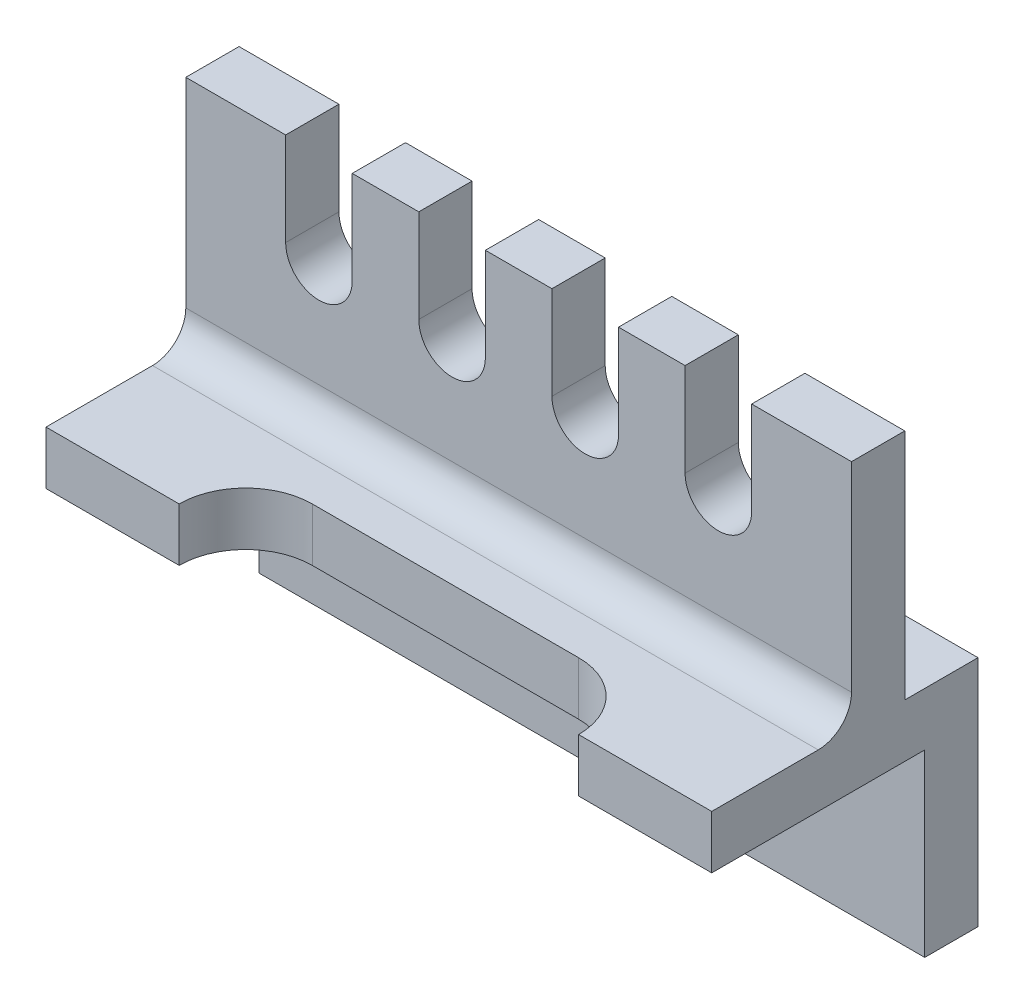
SolidWorks part; units mm, degrees
material "1060 Alloy"
ref_plane "Front Plane" through (0, 0, 0) normal (0, 0, 1) x (1, 0, 0)
ref_plane "Top Plane" through (0, 0, 0) normal (0, 1, 0) x (1, 0, 0)
ref_plane "Right Plane" through (0, 0, 0) normal (1, 0, 0) x (0, 0, -1)
sketch "Sketch1" plane through (0, 0, 0) normal (0, 1, 0) x (1, 0, 0)
  line L1 (0, 0) -> (-100, 0)
  line L2 (0, 0) -> (0, -8)
  line L3 (0, -8) -> (-100, -8)
  line L4 (-100, 0) -> (-100, -8)
  dimension "D1" = 100
  dimension "D2" = 8
extrude "Boss-Extrude1" add sketch "Sketch1" along normal blind 35
sketch "Sketch2" plane through (0, 0, 0) normal (0, 0, 1) x (1, 0, 0)
  line L0 (0, 35) -> (0, 0) construction
  line L1 (-100, 35) -> (0, 35)
  line L2 (-100, 35) -> (-100, 27)
  line L3 (-100, 27) -> (0, 27)
  line L4 (0, 35) -> (0, 27)
  dimension "D1" = 8
extrude "Boss-Extrude2" add sketch "Sketch2" along normal blind 40
sketch "Sketch6" plane through (0, 0, 40) normal (0, 0, 1) x (1, 0, 0)
  line L0 (0, 35) -> (-100, 35) construction
  line L1 (-80, 35) -> (-20, 35)
  line L2 (-80, 35) -> (-80, 27)
  line L3 (-80, 27) -> (-20, 27)
  line L4 (-20, 35) -> (-20, 27)
  line L5 (-100, 27) -> (0, 27) construction
  line L6 (-100, 35) -> (-100, 27) construction
  line L7 (0, 27) -> (0, 35) construction
  dimension "D1" = 20
  dimension "D2" = 20
extrude "Cut-Extrude2" cut sketch "Sketch6" against normal blind 10
fillet "Fillet1" radius 10 2 edges at (-20, 31, 30) (-80, 31, 30)
sketch "Sketch8" plane through (0, 35, 0) normal (0, 1, 0) x (1, 0, 0)
  line L0 (-100, 0) -> (-100, -40) construction
  line L1 (-100, -11) -> (0, -11)
  line L2 (-100, -11) -> (-100, -19)
  line L3 (-100, -19) -> (0, -19)
  line L4 (0, -11) -> (0, -19)
  line L5 (0, -40) -> (0, 0) construction
  line L6 (-80, -40) -> (-100, -40) construction
  dimension "D1" = 8
  dimension "D2" = 21
extrude "Boss-Extrude3" add sketch "Sketch8" along normal blind 35
sketch "Sketch9" plane through (0, 0, 19) normal (0, 0, 1) x (1, 0, 0)
  line L0 (-85, 70) -> (-85, 56)
  line L1 (-100, 70) -> (0, 70) construction
  line L2 (-75, 56) -> (-75, 70)
  line L3 (-85, 70) -> (-75, 70)
  line L4 (-65, 70) -> (-65, 56)
  line L5 (-55, 56) -> (-55, 70)
  line L6 (-65, 70) -> (-55, 70)
  line L7 (-45, 70) -> (-45, 56)
  line L8 (-35, 56) -> (-35, 70)
  line L9 (-45, 70) -> (-35, 70)
  line L10 (-25, 70) -> (-25, 56)
  line L11 (-15, 56) -> (-15, 70)
  line L12 (-25, 70) -> (-15, 70)
  arc A0 (-85, 56) -> (-75, 56) centre (-80, 56) ccw
  arc A1 (-65, 56) -> (-55, 56) centre (-60, 56) ccw
  arc A2 (-45, 56) -> (-35, 56) centre (-40, 56) ccw
  arc A3 (-25, 56) -> (-15, 56) centre (-20, 56) ccw
  point P23 (-58.0103, 70)
  point P24 (-37.9845, 70)
  point P25 (-28.077, 70)
  point P28 (-71.2906, 71.7843)
  dimension "D2" = 5
  dimension "D4" = 5
  dimension "D5" = 5
  dimension "D6" = 5
  dimension "D1" = 14
  dimension "D3" = 20
  dimension "D7" = 14
  dimension "D8" = 14
  dimension "D9" = 14
  dimension "D10" = 20
  dimension "D11" = 20
  dimension "D12" = 20
extrude "Cut-Extrude3" cut sketch "Sketch9" against normal blind 8
fillet "Fillet2" radius 5 1 edges at (-50, 35, 19)
